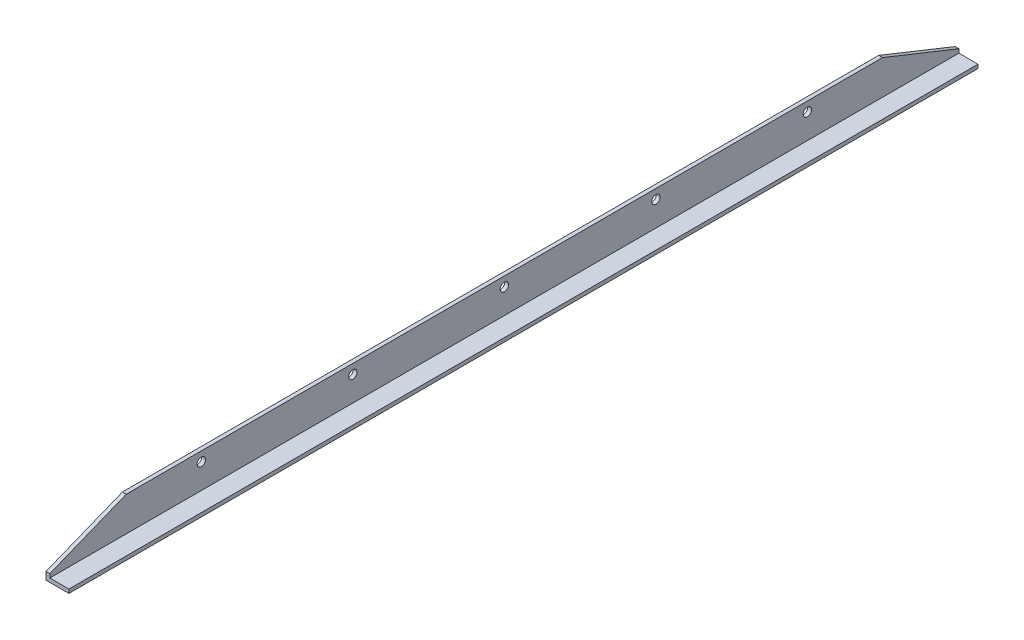
SolidWorks part; units mm, degrees
ref_plane "Front Plane" through (0, 0, 0) normal (0, 0, 1) x (1, 0, 0)
ref_plane "Top Plane" through (0, 0, 0) normal (0, 1, 0) x (1, 0, 0)
ref_plane "Right Plane" through (0, 0, 0) normal (1, 0, 0) x (0, 0, -1)
sketch "Sketch1" plane through (0, 0, 0) normal (0, 0, 1) x (1, 0, 0)
  line L0 (0, 63.5) -> (0, 0)
  line L1 (0, 0) -> (38.1, 0)
  dimension "D1" = 63.5
  dimension "D2" = 38.1
extrude "Extrude-Thin1" add sketch "Sketch1" along normal blind 1511.3 thin thin type one direction reverse wall 6.35
hole_wizard "1/2 Clearance Hole1" positions "Sketch2" profile "Sketch3" hole size "1/2" standard "ANSI Inch"
sketch "Sketch2" plane through (0, 0, 0) normal (-1, 0, 0) x (0, 0, 1)
  line L0 (1511.3, 47.625) -> (1259.4167, 47.625) construction
  line L2 (1259.4167, 47.625) -> (1007.5333, 47.625) construction
  line L3 (1007.5333, 47.625) -> (755.65, 47.625) construction
  line L4 (755.65, 47.625) -> (503.7667, 47.625) construction
  line L5 (503.7667, 47.625) -> (251.8833, 47.625) construction
  line L6 (251.8833, 47.625) -> (0, 47.625) construction
  line L8 (1511.3, 63.5) -> (0, 63.5) construction
  line L9 (0, 63.5) -> (0, 0) construction
  point P0 (1259.4167, 47.625)
  point P2 (1007.5333, 47.625)
  point P4 (755.65, 47.625)
  point P6 (503.7667, 47.625)
  point P8 (251.8833, 47.625)
  point P41 (0, 31.75)
  dimension "D1" = 15.875
sketch "Sketch3" plane through (0, 47.625, 1259.4167) normal (0, 1, 0) x (0, 0, 1)
  line L0 (0, 0) -> (0, 20.6834)
  line L1 (0, 20.6834) -> (6.9456, 16.51)
  line L2 (6.9456, 16.51) -> (6.9456, 0)
  line L5 (6.9456, 0) -> (0, 0)
  line L10 (0, 20.6834) -> (-6.9456, 16.51) construction
  line L11 (0, -6.35) -> (0, 107.95) construction
  dimension "Hole Dia." = 13.8913
  dimension "Hole Depth" = 16.51
  dimension "Drill Angle" = 118
sketch "Sketch4" plane through (0, 0, 0) normal (-1, 0, 0) x (0, 0, 1)
  line L0 (1511.3, 12.7) -> (1384.3, 63.5)
  line L1 (1511.3, 63.5) -> (1511.3, 0) construction
  line L2 (1511.3, 63.5) -> (0, 63.5) construction
  line L3 (1384.3, 63.5) -> (1511.3, 63.5)
  line L4 (1511.3, 63.5) -> (1511.3, 12.7)
  line L5 (127, 63.5) -> (0, 12.7)
  line L6 (0, 63.5) -> (0, 0) construction
  line L7 (0, 12.7) -> (0, 63.5)
  line L8 (0, 63.5) -> (127, 63.5)
  dimension "D1" = 12.7
  dimension "D2" = 127
extrude "Cut-Extrude1" cut sketch "Sketch4" against normal up to surface (6.35 mm away) up to face at (6.35, 47.625, 1252.471)
